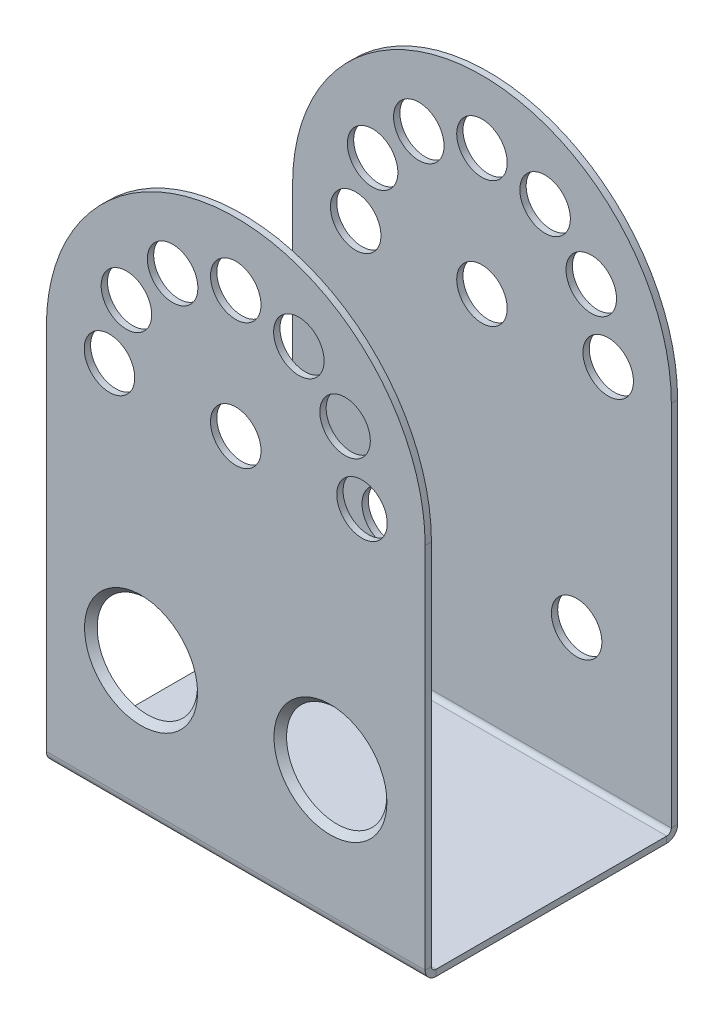
SolidWorks part; units mm, degrees
note: The reader was unsure of these and kept them because the rebuilt part matched: flange length of "Brida de arista1", "Brida de arista2".
material "7075-T6, Chapa (SS)"
ref_plane "Alzado" through (0, 0, 0) normal (0, 0, 1) x (1, 0, 0)
ref_plane "Planta" through (0, 0, 0) normal (0, 1, 0) x (1, 0, 0)
ref_plane "Vista lateral" through (0, 0, 0) normal (1, 0, 0) x (0, 0, -1)
sketch "Croquis1" plane through (0, 0, 0) normal (0, 1, 0) x (1, 0, 0)
  line L1 (-30, 20) -> (30, 20)
  line L2 (-30, 20) -> (-30, -20)
  line L3 (-30, -20) -> (30, -20)
  line L4 (30, 20) -> (30, -20)
  line L5 (-30, 20) -> (30, -20) construction
  line L6 (-30, -20) -> (30, 20) construction
  point P0 (0, 0)
  point P9 (0, 0)
  dimension "D1" = 60
  dimension "D2" = 40
base flange "Brida base2" sketch "Croquis1" thickness 1 reverse thickness direction no parameters "D1"=0.7366
edge flange "Brida de arista1" sketch "Croquis13" flange angle 90 flange length 90 flange position material inside bend radius 0.7366 thickness 1 relief rectangular parameters "D6"=10
sketch "Croquis13" plane through (0, 0, 20) normal (0, 0, -1) x (-1, 0, 0)
  line L2 (-30, 0) -> (-30, 89)
  line L3 (-30, 89) -> (30, 89)
  line L4 (30, 89) -> (30, 0)
  line L5 (30, 0) -> (-30, 0) construction
  line L6 (30, 0) -> (-30, 0)
bend "Pliegue de arista1" bend radius 0.7366 bend angle 90 parameters "D5"=1
edge flange "Brida de arista2" sketch "Croquis16" flange angle 90 flange length 90 flange position material inside bend radius 0.7366 thickness 1 relief rectangular parameters "D6"=10
sketch "Croquis16" plane through (0, 0, -20) normal (0, 0, 1) x (1, 0, 0)
  line L2 (-30, 0) -> (-30, 89)
  line L3 (-30, 89) -> (30, 89)
  line L4 (30, 89) -> (30, 0)
  line L5 (30, 0) -> (-30, 0) construction
  line L6 (30, 0) -> (-30, 0)
bend "Pliegue de arista2" bend radius 0.7366 bend angle 90 parameters "D5"=2
sketch "Croquis17" plane through (0, 0, 20) normal (0, 0, 1) x (1, 0, 0)
  line L0 (0, 59) -> (-10, 76.3205) construction
  line L4 (30, 89) -> (30, 0.7366) construction
  line L5 (0, 59) -> (-17.3205, 69) construction
  line L6 (0, 59) -> (0, 79) construction
  line L7 (0, 59) -> (-20, 59) construction
  line L8 (0, 59) -> (10, 76.3205) construction
  line L9 (30, 89) -> (30, 59) construction
  line L10 (30, 59) -> (-30, 59) construction
  line L11 (30, 59) -> (30, 89)
  line L12 (30, 89) -> (-30, 89)
  line L13 (-30, 89) -> (-30, 59)
  line L14 (0, 59) -> (20, 59) construction
  line L15 (0, 59) -> (17.3205, 69) construction
  arc A6 (30, 59) -> (-30, 59) centre (0, 59) ccw
  circle A7 centre (0, 59) radius 4
  circle A8 centre (20, 59) radius 4
  circle A9 centre (10, 76.3205) radius 4
  circle A10 centre (17.3205, 69) radius 4
  circle A11 centre (0, 79) radius 4
  circle A12 centre (-10, 76.3205) radius 4
  circle A13 centre (-17.3205, 69) radius 4
  circle A14 centre (-20, 59) radius 4
  point P0 (0, 0)
  dimension "D3" = 20
  dimension "D4" = 20
  dimension "D7" = 20
  dimension "D9" = 20
  dimension "D12" = 8
  dimension "D18" = 150
  dimension "D10" = 20
  dimension "D14" = 20
  dimension "D8" = 30
  dimension "D11" = 20
  dimension "D13" = 60
  dimension "D16" = 30
  dimension "D17" = 120
extrude "Cortar-Extruir1" cut sketch "Croquis17" against normal blind 50
sketch "Croquis18" plane through (0, 0, -20) normal (0, 0, -1) x (-1, 0, 0)
  line L0 (0, 0.7366) -> (0, 20.7366) construction
  line L2 (-30, 0.7366) -> (30, 0.7366) construction
  line L4 (-15, 20.7366) -> (15, 20.7366) construction
  circle A0 centre (-15, 20.7366) radius 4
  circle A1 centre (15, 20.7366) radius 4
  point P8 (0, 20.7366)
  dimension "D3" = 8
  dimension "D4" = 8
  dimension "D1" = 20
  dimension "D2" = 30
extrude "Cortar-Extruir2" cut sketch "Croquis18" against normal blind 10
sketch "Croquis19" plane through (0, 0, 20) normal (0, 0, 1) x (1, 0, 0)
  line L0 (0, 0.7366) -> (0, 20.7366) construction
  line L1 (-30, 0.7366) -> (30, 0.7366) construction
  line L2 (-15, 20.7366) -> (15, 20.7366) construction
  circle A0 centre (-15, 20.7366) radius 8.95
  circle A1 centre (15, 20.7366) radius 8.95
  point P8 (0, 20.7366)
  dimension "D3" = 17.9
  dimension "D4" = 17.9
  dimension "D1" = 20
  dimension "D2" = 30
extrude "Cortar-Extruir3" cut sketch "Croquis19" against normal blind 1 draft 45
sketch "Líneas de pliegue3" [suppressed] plane through (0, 0, 0) normal (0, 1, 0) x (1, 0, 0)
sketch "Cuadro delimitador3" [suppressed] plane through (0, 0, 0) normal (0, 1, 0) x (1, 0, 0)
sheet metal parameters "Chapa metálica2" thickness 1 parameters "D1"=0.7366
flat pattern "Chapa desplegada2" [suppressed]
sketch "Líneas de pliegue4" plane through (0, 0, 0) normal (0, 1, 0) x (1, 0, 0)
sketch3d "Cuadro delimitador4" [suppressed]
  line L0 (-30, -25, 0) -> (30, -25, 0) construction
  line L1 (-30, 25, 0) -> (30, 25, 0) construction
  line L2 (-30, -25, 0) -> (-30, 25, 0) construction
  line L3 (30, -25, 0) -> (30, 25, 0) construction
sheet metal parameters "Chapa metálica3" thickness 1 parameters "D1"=0.7366
flat pattern "Chapa desplegada2"
sketch "Líneas de pliegue4" plane through (0, 0, 0) normal (0, 1, 0) x (1, 0, 0)
  line L0 (-30, -24.2346) -> (30, -24.2346) construction
  line L1 (-30, -24.2346) -> (30, -24.2346) construction
sketch3d "Cuadro delimitador4" [suppressed]
  line L0 (-30, 25, 0) -> (-30, -103.4692, 0) construction
  line L1 (30, 25, 0) -> (30, -103.4692, 0) construction
  line L2 (-30, 25, 0) -> (30, 25, 0) construction
  line L3 (-30, -103.4692, 0) -> (30, -103.4692, 0) construction
bend of the flat pattern "Aplanar-<Pliegue de arista1>1"
sheet metal parameters "Chapa metálica4" thickness 1 parameters "D1"=0.7366
flat pattern "Chapa desplegada2"
sketch "Líneas de pliegue4" plane through (0, 0, 0) normal (0, 1, 0) x (1, 0, 0)
  line L0 (-30, -24.2346) -> (30, -24.2346) construction
  line L1 (-30, -24.2346) -> (30, -24.2346) construction
  line L2 (30, 24.2346) -> (-30, 24.2346) construction
  line L3 (30, 24.2346) -> (-30, 24.2346) construction
sketch3d "Cuadro delimitador4" [suppressed]
  line L0 (-30, 103.4692, 0) -> (-30, -103.4692, 0) construction
  line L1 (30, 103.4692, 0) -> (30, -103.4692, 0) construction
  line L2 (-30, 103.4692, 0) -> (30, 103.4692, 0) construction
  line L3 (-30, -103.4692, 0) -> (30, -103.4692, 0) construction
bend of the flat pattern "Aplanar-<Pliegue de arista1>1"
bend of the flat pattern "Aplanar-<Pliegue de arista2>1"
sheet metal parameters "Chapa metálica5" thickness 1 parameters "D1"=0.7366
flat pattern "Chapa desplegada2"
sketch "Líneas de pliegue4" plane through (0, 0, 0) normal (0, 1, 0) x (1, 0, 0)
  line L0 (-30, -19.2346) -> (30, -19.2346) construction
  line L1 (-30, -19.2346) -> (30, -19.2346) construction
  line L2 (30, 19.2346) -> (-30, 19.2346) construction
  line L3 (30, 19.2346) -> (-30, 19.2346) construction
sketch3d "Cuadro delimitador4" [suppressed]
  line L0 (-30, 108.4692, 0) -> (-30, -108.4692, 0) construction
  line L1 (30, 108.4692, 0) -> (30, -108.4692, 0) construction
  line L2 (-30, 108.4692, 0) -> (30, 108.4692, 0) construction
  line L3 (-30, -108.4692, 0) -> (30, -108.4692, 0) construction
bend of the flat pattern "Aplanar-<Pliegue de arista1>1"
bend of the flat pattern "Aplanar-<Pliegue de arista2>1"
sheet metal parameters "Chapa metálica6" thickness 1 parameters "D1"=0.7366
flat pattern "Chapa desplegada6"
sketch "Líneas de pliegue5" plane through (0, 0, 0) normal (0, 1, 0) x (1, 0, 0)
sketch3d "Cuadro delimitador5" [suppressed]
  line L0 (9.5124, 68.7777, 0) -> (8.8425, 66.6384, 0) construction
  line L1 (9.8177, 68.6821, 0) -> (9.1478, 66.5428, 0) construction
  line L2 (9.5124, 68.7777, 0) -> (9.8177, 68.6821, 0) construction
  line L3 (8.8425, 66.6384, 0) -> (9.1478, 66.5428, 0) construction
sheet metal parameters "Chapa metálica7" thickness 1 parameters "D1"=0.7366
flat pattern "Chapa desplegada7"
sketch "Líneas de pliegue6" plane through (0, 0, 0) normal (0, 1, 0) x (1, 0, 0)
sketch "Cuadro delimitador6" [suppressed] plane through (0, 0, 0) normal (0, 1, 0) x (1, 0, 0)
sheet metal parameters "Chapa metálica8" thickness 1 parameters "D1"=0.7366
flat pattern "Chapa desplegada8"
sketch "Líneas de pliegue7" plane through (0, 0, 0) normal (0, 1, 0) x (1, 0, 0)
sketch3d "Cuadro delimitador7" [suppressed]
  line L0 (1.7473, 71.7608, 0) -> (1.5966, 66.1219, 0) construction
  line L1 (4.0732, 71.6986, 0) -> (3.9225, 66.0597, 0) construction
  line L2 (1.7473, 71.7608, 0) -> (4.0732, 71.6986, 0) construction
  line L3 (1.5966, 66.1219, 0) -> (3.9225, 66.0597, 0) construction
sheet metal parameters "Chapa metálica9" thickness 1 parameters "D1"=0.7366
flat pattern "Chapa desplegada9"
sketch "Líneas de pliegue8" plane through (0, 0, 0) normal (0, 1, 0) x (1, 0, 0)
sketch "Cuadro delimitador8" [suppressed] plane through (0, 0, 0) normal (0, 1, 0) x (1, 0, 0)
sheet metal parameters "Chapa metálica10" thickness 1 parameters "D1"=0.7366
flat pattern "Chapa desplegada10"
sketch "Líneas de pliegue9" plane through (0, 0, 0) normal (0, 1, 0) x (1, 0, 0)
sketch "Cuadro delimitador9" [suppressed] plane through (0, 0, 0) normal (0, 1, 0) x (1, 0, 0)
sheet metal parameters "Chapa metálica11" thickness 1 parameters "D1"=0.7366
flat pattern "Chapa desplegada11"
sketch "Líneas de pliegue10" plane through (0, 0, 0) normal (0, 1, 0) x (1, 0, 0)
sketch "Cuadro delimitador10" [suppressed] plane through (0, 0, 0) normal (0, 1, 0) x (1, 0, 0)
sheet metal parameters "Chapa metálica12" thickness 1 parameters "D1"=0.7366
flat pattern "Chapa desplegada12"
sketch "Líneas de pliegue11" plane through (0, 0, 0) normal (0, 1, 0) x (1, 0, 0)
sketch "Cuadro delimitador11" [suppressed] plane through (0, 0, 0) normal (0, 1, 0) x (1, 0, 0)
sheet metal parameters "Chapa metálica13" thickness 1 parameters "D1"=0.7366
flat pattern "Chapa desplegada13"
sketch "Líneas de pliegue12" plane through (0, 0, 0) normal (0, 1, 0) x (1, 0, 0)
sketch "Cuadro delimitador12" [suppressed] plane through (0, 0, 0) normal (0, 1, 0) x (1, 0, 0)
sheet metal parameters "Chapa metálica14" thickness 1 parameters "D1"=0.7366
flat pattern "Chapa desplegada2"
sketch "Líneas de pliegue4" plane through (0, 0, 0) normal (0, 1, 0) x (1, 0, 0)
  line L0 (-30, -19.2346) -> (30, -19.2346) construction
  line L1 (-30, -19.2346) -> (30, -19.2346) construction
  line L2 (30, 19.2346) -> (-30, 19.2346) construction
  line L3 (30, 19.2346) -> (-30, 19.2346) construction
sketch3d "Cuadro delimitador4" [suppressed]
  line L0 (-30, 108.4692, 0) -> (-30, -108.4692, 0) construction
  line L1 (30, 108.4692, 0) -> (30, -108.4692, 0) construction
  line L2 (-30, 108.4692, 0) -> (30, 108.4692, 0) construction
  line L3 (-30, -108.4692, 0) -> (30, -108.4692, 0) construction
bend of the flat pattern "Aplanar-<Pliegue de arista1>1"
bend of the flat pattern "Aplanar-<Pliegue de arista2>1"
sheet metal parameters "Chapa metálica15" thickness 1 parameters "D1"=0.7366
flat pattern "Chapa desplegada2"
sketch "Líneas de pliegue4" plane through (0, 0, 0) normal (0, 1, 0) x (1, 0, 0)
  line L0 (-30, -19.2346) -> (30, -19.2346) construction
  line L1 (-30, -19.2346) -> (30, -19.2346) construction
  line L2 (30, 19.2346) -> (-30, 19.2346) construction
  line L3 (30, 19.2346) -> (-30, 19.2346) construction
sketch3d "Cuadro delimitador4" [suppressed]
  line L0 (-30, 108.4692, 0) -> (-30, -108.4692, 0) construction
  line L1 (30, 108.4692, 0) -> (30, -108.4692, 0) construction
  line L2 (-30, 108.4692, 0) -> (30, 108.4692, 0) construction
  line L3 (-30, -108.4692, 0) -> (30, -108.4692, 0) construction
bend of the flat pattern "Aplanar-<Pliegue de arista1>1"
bend of the flat pattern "Aplanar-<Pliegue de arista2>1"
